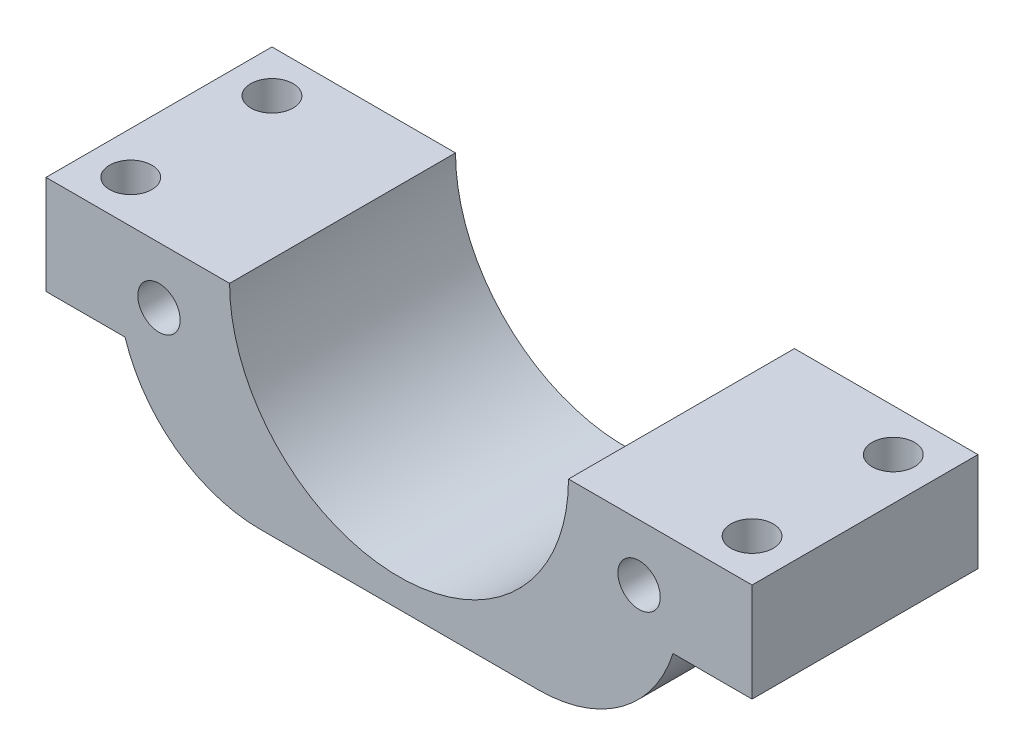
SolidWorks part; units mm, degrees
ref_plane "Front Plane" through (0, 0, 0) normal (0, 0, 1) x (1, 0, 0)
ref_plane "Top Plane" through (0, 0, 0) normal (0, 1, 0) x (1, 0, 0)
ref_plane "Right Plane" through (0, 0, 0) normal (1, 0, 0) x (0, 0, -1)
sketch "Sketch7" plane through (0, 0, 0) normal (0, 0, 1) x (1, 0, 0)
  line L17 (5.5981, 0.9) -> (44.4, 0.9)
  line L20 (0, 14.9) -> (13, 14.9)
  line L21 (37, 14.9) -> (50, 14.9)
  line L22 (5.5981, 16.7) -> (5.5981, 14.9)
  line L24 (5.5981, 7.9) -> (0, 7.9)
  line L25 (5.5981, 7.9) -> (5.5981, 0.9)
  line L26 (44.4, 7.9) -> (44.4, 0.9)
  line L29 (50, 7.9) -> (44.4, 7.9)
  line L31 (50, 14.9) -> (50, 7.9)
  line L32 (0, 14.9) -> (0, 7.9)
  circle A1 centre (8, 10.9) radius 1.5
  circle A2 centre (42, 10.9) radius 1.5
  arc A3 (13, 14.9) -> (37, 14.9) centre (25, 14.9) ccw
  dimension "D3" = 5.5981
  dimension "D10" = 7
  dimension "D11" = 3
  dimension "D12" = 5.6
  dimension "D13" = 7
  dimension "D15" = 3
  dimension "D7" = 13
  dimension "D8" = 4
  dimension "D2" = 24
  dimension "D9" = 4
  dimension "D14" = 7
extrude "Boss-Extrude11" add sketch "Sketch7" along normal blind 16 contours A3 L20 L32 L24 L25 L17 L26 L29 L31 L21 A2 A1 region at (6.1173, 4.4, 0)
ref_plane "Plane2" through (0, 7.9, 0) normal (0, -1, 0) x (-1, 0, 0)
sketch "Sketch8" plane through (0, 7.9, 0) normal (0, -1, 0) x (1, 0, 0)
  line L8 (0, 0) -> (13, 0) construction
  line L9 (0, 16) -> (0, 0) construction
  line L11 (0, 16) -> (13, 16) construction
  line L12 (50, 16) -> (50, 0) construction
  line L13 (37, 0) -> (50, 0) construction
  line L14 (37, 16) -> (50, 16) construction
  circle A0 centre (3, 13) radius 1.5
  circle A1 centre (47, 13) radius 1.5
  circle A2 centre (47, 3) radius 1.5
  circle A3 centre (3, 3) radius 1.5
  dimension "D1" = 3
  dimension "D2" = 3
  dimension "D3" = 3
  dimension "D4" = 3
  dimension "D5" = 3
  dimension "D6" = 3
  dimension "D7" = 3
  dimension "D8" = 3
  dimension "D9" = 3
extrude "Cut-Extrude1" cut sketch "Sketch8" against normal through all
fillet "Fillet1" radius 10 2 edges at (5.5981, 0.9, 8) (44.4, 0.9, 8)
